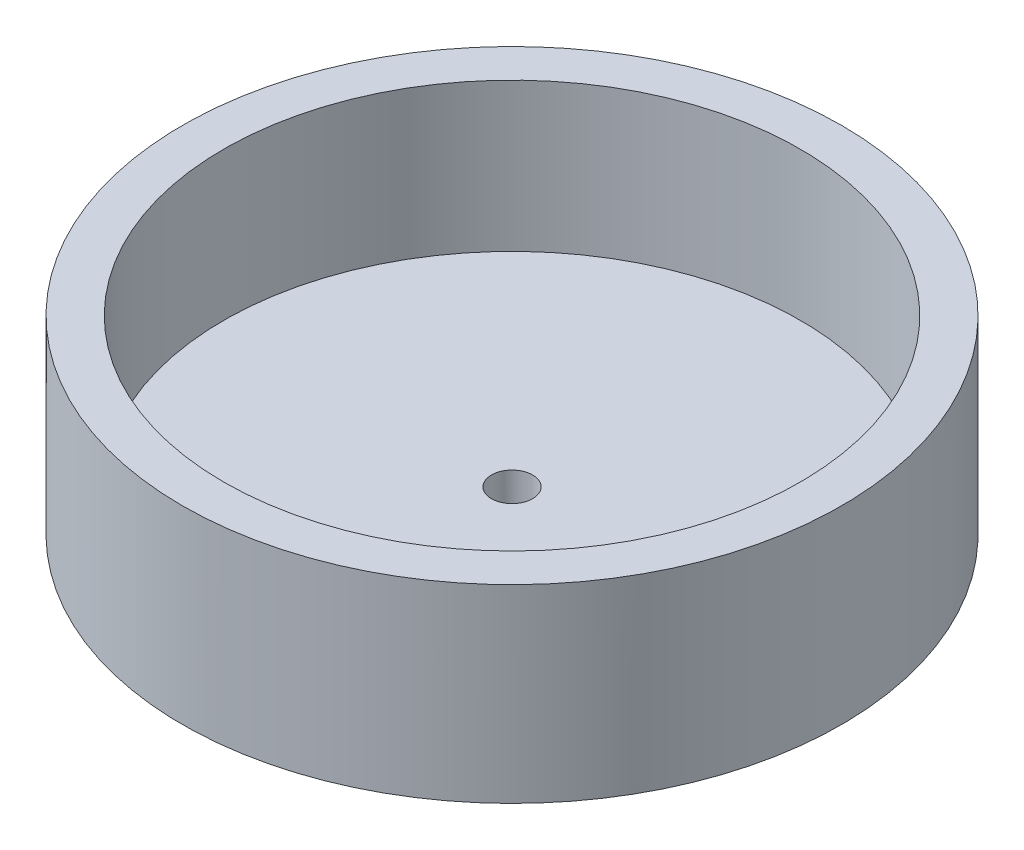
SolidWorks part; units mm, degrees
ref_plane "Plan de face" through (0, 0, 0) normal (0, 0, 1) x (1, 0, 0)
ref_plane "Plan de dessus" through (0, 0, 0) normal (0, 1, 0) x (1, 0, 0)
ref_plane "Plan de droite" through (0, 0, 0) normal (1, 0, 0) x (0, 0, -1)
sketch "Esquisse1" plane through (0, 0, 0) normal (0, 1, 0) x (1, 0, 0)
  circle A0 centre (0, 0) radius 40
extrude "Boss.-Extru.2" add sketch "Esquisse1" along normal blind 35
sketch "Esquisse4" plane through (0, 35, 0) normal (0, 1, 0) x (1, 0, 0)
  circle A0 centre (0, 0) radius 35
extrude "Enlèv. mat.-Extru.2" cut sketch "Esquisse4" against normal blind 18
sketch "Esquisse5" plane through (0, 0, 0) normal (0, -1, 0) x (-1, 0, 0)
  circle A0 centre (0, 0) radius 40
sketch "Esquisse6" plane through (0, 17, 0) normal (0, 1, 0) x (1, 0, 0)
  circle A0 centre (0, 0) radius 2.5
extrude "Enlèv. mat.-Extru.4" cut sketch "Esquisse6" against normal blind 12
extrude "Enlèv. mat.-Extru.5" cut sketch "Esquisse5" against normal blind 12
